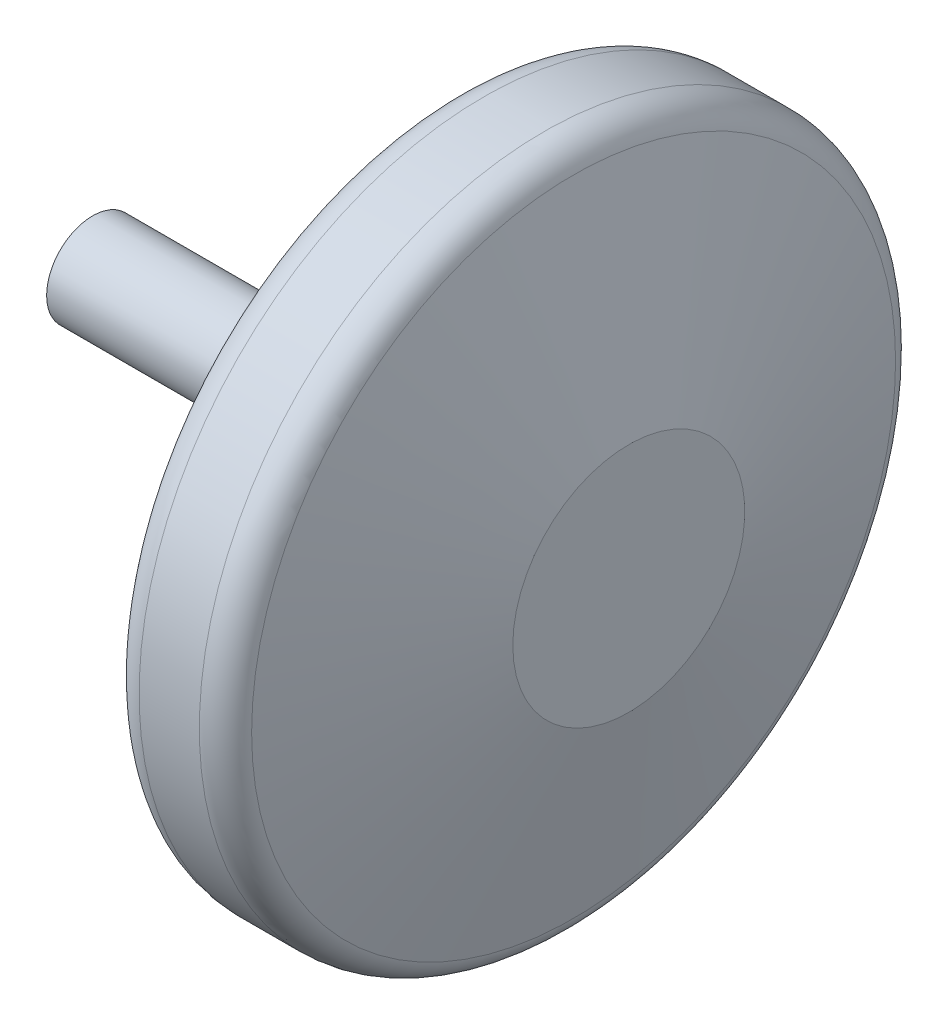
SolidWorks part; units mm, degrees
material "Полиамид ПА-6Б ТУ 6-05-988-87"
ref_plane "Plane1" through (0, 0, 0) normal (0, 0, 1) x (1, 0, 0)
ref_plane "Plane2" through (0, 0, 0) normal (0, 1, 0) x (1, 0, 0)
ref_plane "Plane3" through (0, 0, 0) normal (1, 0, 0) x (0, 0, -1)
sketch "Эскиз1" plane through (0, 0, 0) normal (0, 0, 1) x (1, 0, 0)
  line L0 (0, 0) -> (39.5937, 0) construction
  line L1 (0, 0) -> (0, 3)
  line L2 (0, 3) -> (20, 3)
  line L3 (20, 3) -> (20, 7.5718)
  line L5 (20, 7.5718) -> (24, 22.5)
  line L6 (24, 22.5) -> (31, 22.5)
  line L7 (31, 22.5) -> (31, 14) construction
  line L8 (31, 14) -> (26, 9) construction
  line L9 (26, 9) -> (26, 0) construction
  line L10 (0, 0) -> (26, 0)
  line L11 (31, 22.5) -> (35, 7.5718)
  line L12 (35, 7.5718) -> (35, 0)
  line L13 (35, 0) -> (26, 0)
  line L14 (20, 7.5718) -> (35, 7.5718) construction
  line L15 (27.5, 7.5718) -> (27.5, 32.6044) construction
  dimension "D3" = 20
  dimension "D4" = 15
  dimension "D2" = 6
  dimension "D5" = 15
  dimension "D6" = 45
  dimension "D7" = 7
  dimension "D8" = 5
  dimension "D9" = 28
  dimension "D10" = 18
  dimension "D11" = 35
revolve "Повернуть1" add sketch "Эскиз1" angle 360 about L0
fillet "Скругление1" radius 2 2 edges at (24, 0, 22.5) (31, 0, 22.5)
